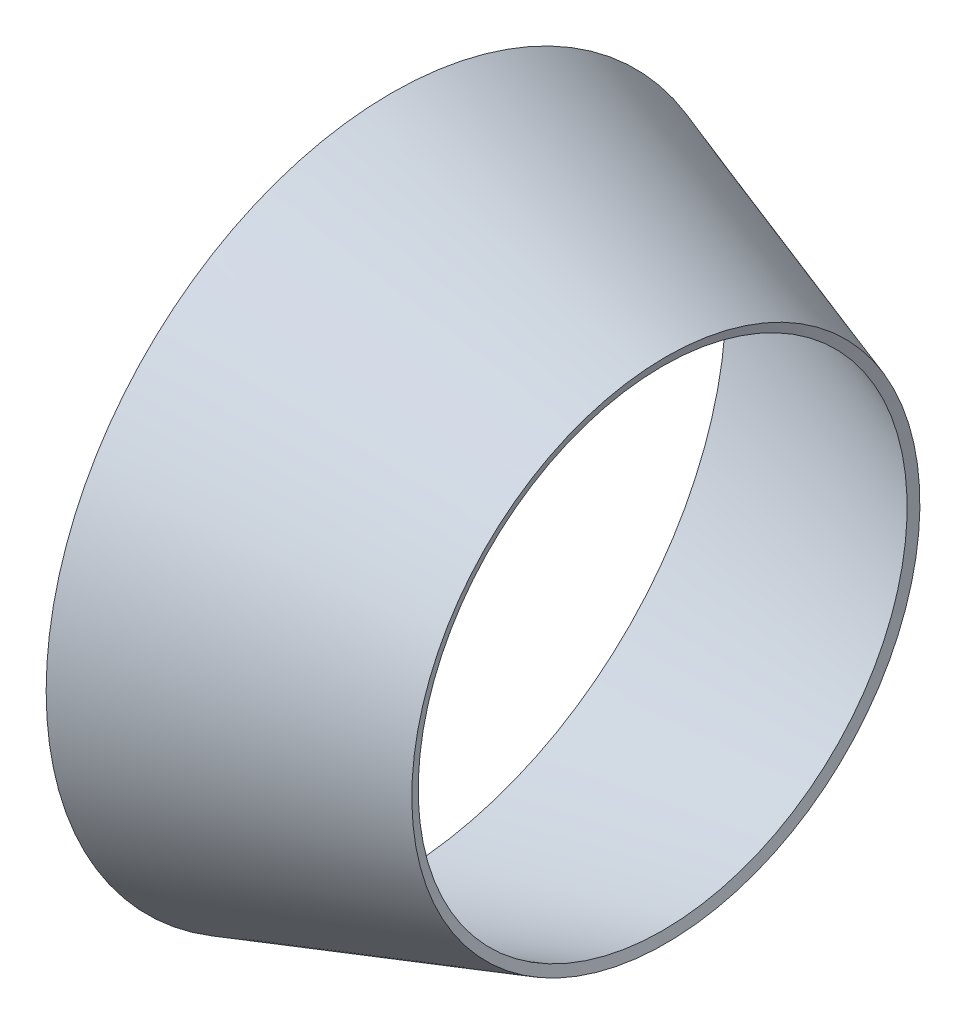
SolidWorks part; units mm, degrees
ref_plane "Front Plane" through (0, 0, 0) normal (0, 0, 1) x (1, 0, 0)
ref_plane "Top Plane" through (0, 0, 0) normal (0, 1, 0) x (1, 0, 0)
ref_plane "Right Plane" through (0, 0, 0) normal (1, 0, 0) x (0, 0, -1)
sketch "Sketch1" plane through (0, 0, 0) normal (0, 0, 1) x (1, 0, 0)
  line L0 (-42.0913, -43.4233) -> (-7.5764, -31.9503)
  line L1 (-42.0913, -47.5161) -> (-42.0913, 47.5161) construction
  line L2 (-7.5764, -31.9503) -> (-7.977, -30.7451)
  line L3 (-7.977, -30.7451) -> (-42.0913, -42.085)
  line L4 (-42.0913, -45.72) -> (-42.0913, 45.72) construction
  line L5 (0, 0) -> (-88.1772, 0) construction
  line L6 (-129.4673, 0) -> (-46.8871, 0) construction
  line L7 (-42.0913, -43.4233) -> (-42.0913, -42.085)
  dimension "D1" = 1.27
revolve "Revolve1" add sketch "Sketch1" angle 360 about L5
